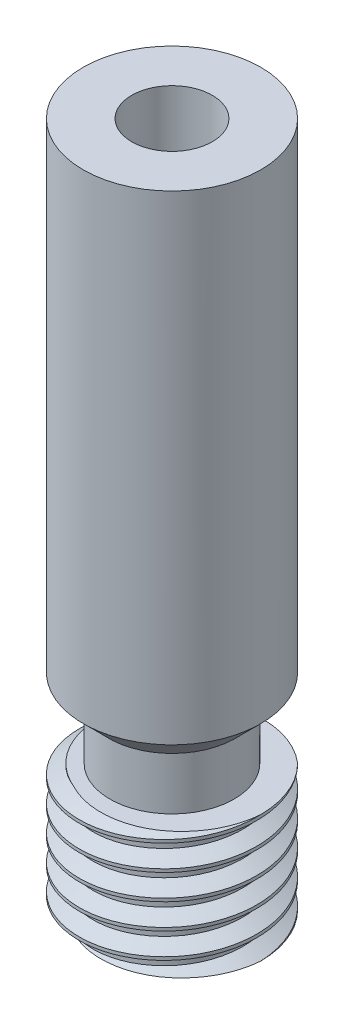
SolidWorks part; units mm, degrees
material "201 Acero inoxidable recocido (SS)"
ref_plane "Alzado" through (0, 0, 0) normal (0, 0, 1) x (1, 0, 0)
ref_plane "Planta" through (0, 0, 0) normal (0, 1, 0) x (1, 0, 0)
ref_plane "Vista lateral" through (0, 0, 0) normal (1, 0, 0) x (0, 0, -1)
sketch "Croquis2" plane through (0, 0, 0) normal (0, 1, 0) x (1, 0, 0)
  circle A0 centre (0, 0) radius 3.5
  dimension "D1" = 7
extrude "Saliente-Extruir1" add sketch "Croquis2" along normal blind 27
thread "Rosca1" pitch 1 method cut profile "Perfil de rosca1" start angle 0, offset 1, length 6, pitch 1, diameter 7
ref_plane "Plano1" through (3.5, -1, 0) normal (0, 0, 1) x (1, 0, 0)
sketch "Perfil de rosca1" plane through (3.5, -1, 0) normal (0, 0, 1) x (1, 0, 0)
  line L0 (0, 0) -> (0, 1) construction
  line L11 (0, 0) -> (0, 0.875)
  line L12 (0, 0.875) -> (-0.5413, 0.5625)
  line L13 (-0.5413, 0.5625) -> (-0.5413, 0.3125)
  line L15 (-0.5413, 0.3125) -> (0, 0)
  line L17 (-0.5413, 0.4375) -> (0, 0.4375) construction
  point P2 (0, 0)
  dimension "Pitch" = 1
  dimension "Profile_Angle" = 60
  dimension "Profile_Land" = 0.25
  dimension "Profile_Height" = 0.5413
ref_plane "Plano2" through (0, 5, 0) normal (0, -1, 0) x (-1, 0, 0)
sketch "Croquis5" plane through (0, 5, 0) normal (0, -1, 0) x (-1, 0, 0)
  circle A0 centre (0, 0) radius 2.45
  dimension "D1" = 4.9
extrude "Cortar-Extruir-Lámina1" cut sketch "Croquis5" against normal blind 2.1 thin thin type one direction wall 10
sketch "Croquis6" plane through (0, 27, 0) normal (0, 1, 0) x (1, 0, 0)
  circle A0 centre (0, 0) radius 1.2
  dimension "D1" = 2.4
extrude "Cortar-Extruir1" cut sketch "Croquis6" against normal through all
chamfer "Chaflán1" distance 1 angle 45 1 edges at (0, 7.1, -3.5)
sketch "Croquis8" plane through (0, 27, 0) normal (0, 1, 0) x (1, 0, 0)
  circle A0 centre (0, 0) radius 1.5875
  dimension "D1" = 3.175
extrude "Cortar-Extruir2" cut sketch "Croquis8" against normal blind 5
chamfer "Chaflán2" distance 1 angle 45 1 edges at (0, 22, 1.2)
